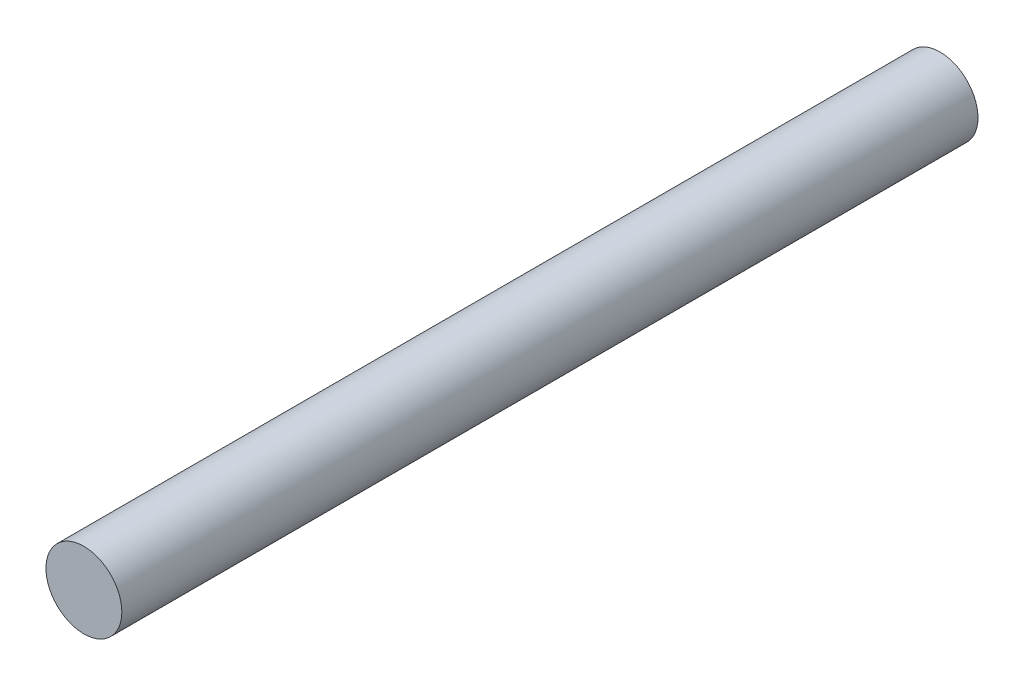
SolidWorks part; units mm, degrees
ref_plane "Front Plane" through (0, 0, 0) normal (0, 0, 1) x (1, 0, 0)
ref_plane "Top Plane" through (0, 0, 0) normal (0, 1, 0) x (1, 0, 0)
ref_plane "Right Plane" through (0, 0, 0) normal (1, 0, 0) x (0, 0, -1)
sketch "Croquis1" plane through (0, 0, 0) normal (0, 0, 1) x (1, 0, 0)
  line L0 (0, 0) -> (16.5, 28.5788) construction
  line L1 (0, 0) -> (24, 0) construction
  line L2 (16.5, 28.5788) -> (58.4988, 28.8934) construction
  line L3 (58.4988, 28.8934) -> (24, 0) construction
  line L4 (24, 0) -> (156.3209, 0) construction
  line L5 (58.4988, 28.8934) -> (156.3209, 0) construction
  line L6 (24, 0) -> (185.7, 0) construction
  line L7 (24, 0) -> (75.3, 0) construction
  circle A0 centre (0, 0) radius 2 construction
  circle A1 centre (0, 0) radius 0.665 construction
  dimension "D9" = 4
  dimension "D10" = 1.33
  dimension "D1" = 24
  dimension "D2" = 33
  dimension "D3" = 42
  dimension "D4" = 45
  dimension "D5" = 102
  dimension "D6" = 161.7
  dimension "D7" = 51.3
  dimension "D8" = 60
sketch "Croquis4" plane through (0, 0, 0) normal (0, 0, 1) x (1, 0, 0)
  line L0 (16.5, 28.5788) -> (58.4988, 28.8934) construction
  line L1 (16.485, 30.5788) -> (58.4838, 30.8934)
  line L2 (16.515, 26.5789) -> (58.5138, 26.8935)
  arc A0 (16.485, 30.5788) -> (16.515, 26.5789) centre (16.5, 28.5788) ccw
  arc A1 (58.5138, 26.8935) -> (58.4838, 30.8934) centre (58.4988, 28.8934) ccw
  circle A2 centre (16.5, 28.5788) radius 0.665
  circle A3 centre (58.4988, 28.8934) radius 0.665
  circle A4 centre (0, 0) radius 0.665 construction
  circle A5 centre (0, 0) radius 2 construction
  point P4 (37.4994, 28.7361)
sketch "Croquis3" plane through (0, 0, 0) normal (0, 0, 1) x (1, 0, 0)
  line L0 (0, 0) -> (16.5, 28.5788) construction
  line L1 (-1.7321, 1) -> (14.7679, 29.5788)
  line L2 (1.7321, -1) -> (18.2321, 27.5788)
  arc A0 (-1.7321, 1) -> (1.7321, -1) centre (0, 0) ccw
  arc A1 (18.2321, 27.5788) -> (14.7679, 29.5788) centre (16.5, 28.5788) ccw
  circle A2 centre (16.5, 28.5788) radius 0.6667
  circle A3 centre (0, 0) radius 0.6667
  circle A4 centre (0, 0) radius 2 construction
  point P4 (8.25, 14.2894)
  dimension "D2" = 1.3333
extrude "Saliente-Extruir1" [suppressed] add sketch "Croquis3" along normal blind 5
extrude "Saliente-Extruir2" [suppressed] add sketch "Croquis4" along normal blind 5
sketch "Croquis5" plane through (0, 0, 0) normal (0, 0, 1) x (1, 0, 0)
  line L0 (24, 0) -> (58.4988, 28.8934) construction
  line L1 (22.7158, 1.5333) -> (57.2147, 30.4267)
  line L2 (25.2842, -1.5333) -> (59.783, 27.3602)
  arc A0 (22.7158, 1.5333) -> (25.2842, -1.5333) centre (24, 0) ccw
  arc A1 (59.783, 27.3602) -> (57.2147, 30.4267) centre (58.4988, 28.8934) ccw
  circle A2 centre (0, 0) radius 2 construction
  circle A3 centre (24, 0) radius 0.665
  circle A4 centre (58.4988, 28.8934) radius 1.0102
  circle A5 centre (0, 0) radius 0.665 construction
  point P4 (41.2494, 14.4467)
extrude "Saliente-Extruir3" [suppressed] add sketch "Croquis5" along normal blind 5
sketch "Croquis6" plane through (0, 0, 0) normal (0, 0, 1) x (1, 0, 0)
  line L0 (58.4988, 28.8934) -> (156.3209, 0) construction
  line L1 (59.0654, 30.8115) -> (156.8875, 1.9181)
  line L2 (57.9323, 26.9754) -> (155.7544, -1.9181)
  arc A0 (59.0654, 30.8115) -> (57.9323, 26.9754) centre (58.4988, 28.8934) ccw
  arc A1 (155.7544, -1.9181) -> (156.8875, 1.9181) centre (156.3209, 0) ccw
  circle A2 centre (58.4988, 28.8934) radius 0.665
  circle A3 centre (156.3209, 0) radius 0.665
  circle A4 centre (0, 0) radius 0.665 construction
  circle A5 centre (0, 0) radius 2 construction
  point P4 (107.4099, 14.4467)
extrude "Saliente-Extruir4" [suppressed] add sketch "Croquis6" along normal blind 5
sketch "Croquis8" plane through (0, 0, 0) normal (0, 0, 1) x (1, 0, 0)
  line L0 (0, 0) -> (0, 4) construction
  line L1 (0, 0) -> (-4, 0) construction
  line L2 (-4, 0) -> (-4, -4)
  line L3 (-4, -4) -> (185.7, -4)
  line L4 (185.7, 0) -> (185.7, -4) construction
  line L5 (185.7, -4) -> (189.7, -4)
  line L6 (189.7, -4) -> (189.7, 0)
  line L7 (185.7, 0) -> (185.7, 4) construction
  line L8 (185.7, 4) -> (0, 4)
  line L9 (75.3, 0) -> (185.7, 0) construction
  line L10 (75.3, 0.665) -> (185.7, 0.665)
  line L11 (75.3, -0.665) -> (185.7, -0.665)
  line L12 (24, 0) -> (185.7, 0) construction
  arc A0 (0, 4) -> (-4, 0) centre (0, 0) ccw
  arc A1 (189.7, 0) -> (185.7, 4) centre (185.7, 0) ccw
  circle A2 centre (0, 0) radius 0.665 construction
  circle A3 centre (0, 0) radius 0.665
  circle A4 centre (24, 0) radius 0.665
  arc A5 (75.3, 0.665) -> (75.3, -0.665) centre (75.3, 0) ccw
  arc A6 (185.7, -0.665) -> (185.7, 0.665) centre (185.7, 0) ccw
  point P20 (130.5, 0)
  dimension "D1" = 4
extrude "Saliente-Extruir5" [suppressed] add sketch "Croquis8" against normal blind 5
sketch "Croquis9" plane through (0, 0, 0) normal (0, 0, 1) x (1, 0, 0)
  circle A0 centre (156.3209, 0) radius 0.665
  circle A1 centre (0, 0) radius 0.665 construction
extrude "Saliente-Extruir6" add sketch "Croquis9" along normal blind 5 and the other way blind 10
sketch "Croquis10" [suppressed] plane through (0, 0, 0) normal (0, 0, 1) x (1, 0, 0)
  circle A0 centre (16.5, 28.5788) radius 0.665
  circle A1 centre (0, 0) radius 0.665 construction
extrude "Saliente-Extruir7" [suppressed] add sketch "Croquis10" along normal blind 5 and the other way blind 5
equation "\"LD\"=24"
equation "\"D1@Croquis1\"=\"LD\""
equation "\"LA\"=33"
equation "\"D2@Croquis1\"=\"LA\""
equation "\"LB\"=42"
equation "\"D3@Croquis1\"=\"LB\""
equation "\"LC\"=45"
equation "\"D4@Croquis1\"=\"LC\""
equation "\"LE\"=102"
equation "\"D5@Croquis1\"=\"LE\""
equation "\"Lf\"= \"LC\" + \"LE\""
equation "\"Lo\"= \"LE\" - \"LC\""
equation "\"D7@Croquis1\"=\"Lo\"*0.9"
equation "\"D6@Croquis1\"=\"Lf\"*1.1"
equation "\"D2\"= ( \"LA\" + \"LB\" + \"LC\" ) / 3 * 0.1"
equation "\"D1\"= \"D2\" / 3"
equation "\"D2@Croquis3\"=\"D1\""
equation "\"ancho\"=5"
equation "\"D1@Saliente-Extruir1\"=\"ancho\""
equation "\"D1@Saliente-Extruir2\"=\"ancho\""
equation "\"D1@Saliente-Extruir3\"=\"ancho\""
equation "\"D1@Saliente-Extruir4\"=\"ancho\""
equation "\"D1@Croquis8\"=\"D2\""
equation "\"D1@Saliente-Extruir5\"=\"ancho\""
equation "\"D1@Saliente-Extruir6\"=\"ancho\""
equation "\"D2@Saliente-Extruir6\"=\"ancho\"*2"
equation "\"D1@Saliente-Extruir7\"=\"ancho\""
equation "\"D2@Saliente-Extruir7\"=\"ancho\""
